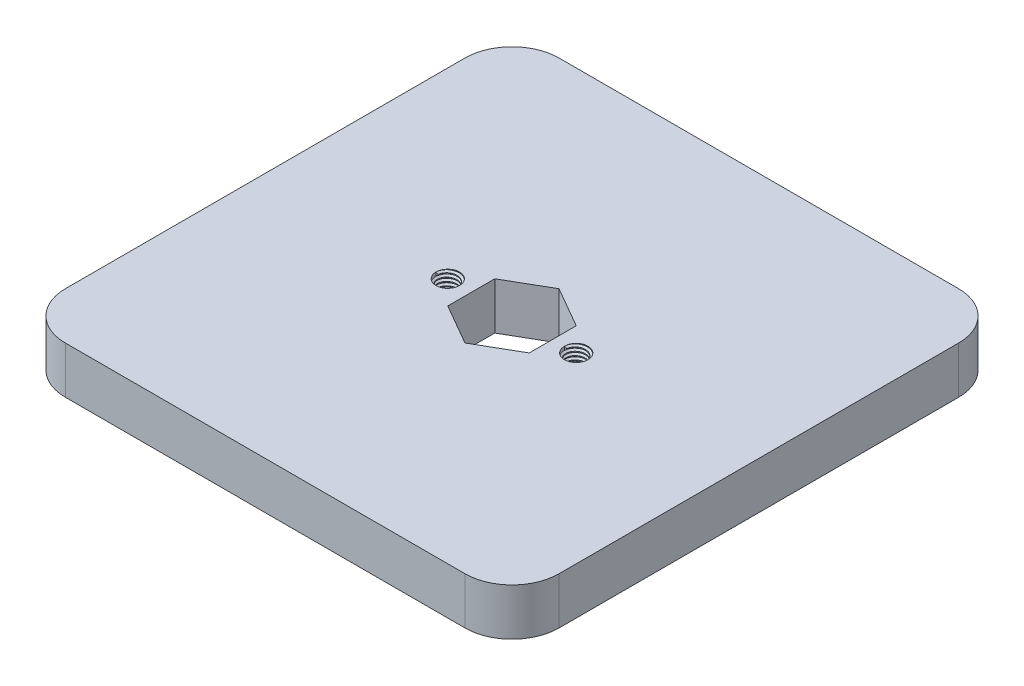
SolidWorks part; units mm, degrees
ref_plane "Front Plane" through (0, 0, 0) normal (0, 0, 1) x (1, 0, 0)
ref_plane "Top Plane" through (0, 0, 0) normal (0, 1, 0) x (1, 0, 0)
ref_plane "Right Plane" through (0, 0, 0) normal (1, 0, 0) x (0, 0, -1)
sketch "Sketch1" plane through (0, 0, 0) normal (0, 1, 0) x (1, 0, 0)
  line L0 (-13.6603, 0) -> (13.6603, 0) construction
  line L1 (0, 10) -> (-8.6603, 5)
  line L2 (-8.6603, 5) -> (-8.6603, -5)
  line L3 (-8.6603, -5) -> (0, -10)
  line L4 (0, -10) -> (8.6603, -5)
  line L5 (8.6603, -5) -> (8.6603, 5)
  line L6 (8.6603, 5) -> (0, 10)
  line L7 (-52.5, -52.5) -> (52.5, -52.5)
  line L8 (-52.5, -52.5) -> (-52.5, 52.5)
  line L9 (-52.5, 52.5) -> (52.5, 52.5)
  line L10 (52.5, -52.5) -> (52.5, 52.5)
  line L11 (-52.5, -52.5) -> (52.5, 52.5) construction
  line L12 (-52.5, 52.5) -> (52.5, -52.5) construction
  circle A0 centre (0, 0) radius 8.6603 construction
  circle A1 centre (-13.6603, 0) radius 2.5
  circle A2 centre (13.6603, 0) radius 2.5
  point P17 (0, 0)
  point P18 (14.1404, 0)
  point P19 (0, 0)
  point P20 (0, 0)
  point P21 (0, 0)
  dimension "D1" = 5
  dimension "D2" = 5
  dimension "D3" = 105
  dimension "D4" = 10
extrude "Boss-Extrude1" add sketch "Sketch1" along normal blind 10
fillet "Fillet1" radius 10 4 edges at (52.5, 5, -52.5) (-52.5, 5, -52.5) (52.5, 5, 52.5) (-52.5, 5, 52.5)
thread "Thread1" pitch 0.8 method extrude profile "Thread Profile1" start angle 0, offset 0, length 10, pitch 0.8, diameter 5
ref_plane "Plane1" through (-16.1603, 10, 0) normal (0, 0, 1) x (-1, 0, 0)
sketch "Thread Profile1" plane through (-16.1603, 10, 0) normal (0, 0, 1) x (-1, 0, 0)
  line L0 (0, 0) -> (0, 0.8) construction
  line L11 (0, 0) -> (0, 0.7)
  line L12 (0, 0.7) -> (-0.433, 0.45)
  line L13 (-0.433, 0.45) -> (-0.433, 0.25)
  line L15 (-0.433, 0.25) -> (0, 0)
  line L17 (-0.433, 0.35) -> (0, 0.35) construction
  point P2 (0, 0)
  dimension "Pitch" = 0.8
  dimension "Profile_Angle" = 60
  dimension "Profile_Land" = 0.2
  dimension "Profile_Height" = 0.433
thread "Thread2" pitch 0.8 method extrude profile "Thread Profile2" start angle 0, offset 0, length 10, pitch 0.8, diameter 5
ref_plane "Plane2" through (11.1603, 10, 0) normal (0, 0, 1) x (-1, 0, 0)
sketch "Thread Profile2" plane through (11.1603, 10, 0) normal (0, 0, 1) x (-1, 0, 0)
  line L0 (0, 0) -> (0, 0.8) construction
  line L11 (0, 0) -> (0, 0.7)
  line L12 (0, 0.7) -> (-0.433, 0.45)
  line L13 (-0.433, 0.45) -> (-0.433, 0.25)
  line L15 (-0.433, 0.25) -> (0, 0)
  line L17 (-0.433, 0.35) -> (0, 0.35) construction
  point P2 (0, 0)
  dimension "Pitch" = 0.8
  dimension "Profile_Angle" = 60
  dimension "Profile_Land" = 0.2
  dimension "Profile_Height" = 0.433
